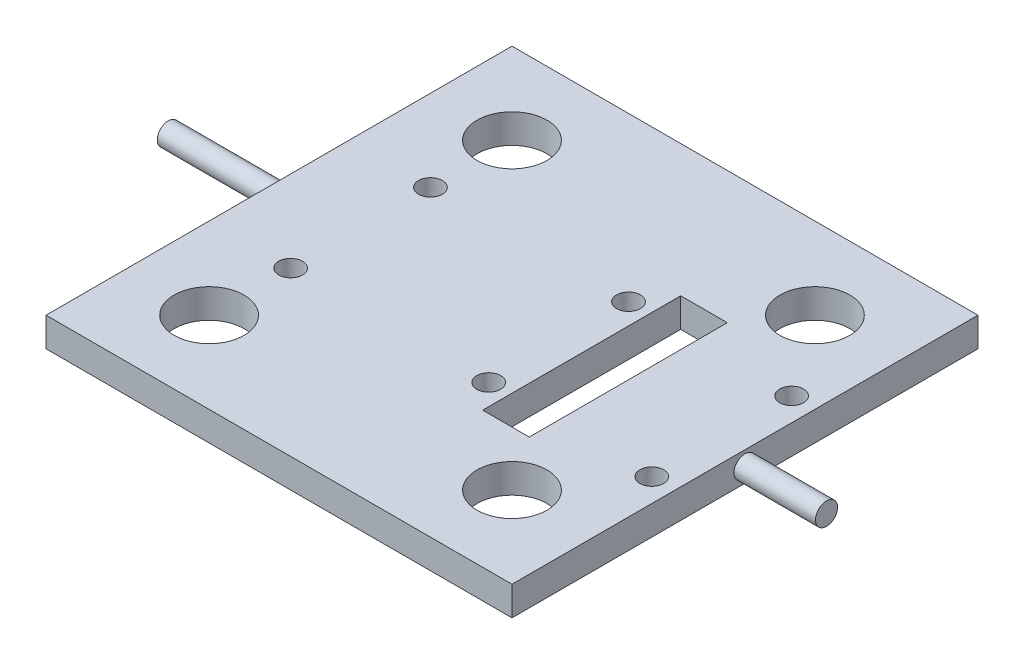
SolidWorks part; units mm, degrees
ref_plane "Front Plane" through (0, 0, 0) normal (0, 0, 1) x (1, 0, 0)
ref_plane "Top Plane" through (0, 0, 0) normal (0, 1, 0) x (1, 0, 0)
ref_plane "Right Plane" through (0, 0, 0) normal (1, 0, 0) x (0, 0, -1)
sketch "Sketch1" plane through (0, 0, 0) normal (0, 1, 0) x (1, 0, 0)
  line L1 (-25.4, -25.4) -> (25.4, -25.4)
  line L2 (-25.4, -25.4) -> (-25.4, 25.4)
  line L3 (-25.4, 25.4) -> (25.4, 25.4)
  line L4 (25.4, -25.4) -> (25.4, 25.4)
  line L5 (-25.4, -25.4) -> (25.4, 25.4) construction
  line L6 (-25.4, 25.4) -> (25.4, -25.4) construction
  point P0 (0, 0)
  dimension "D1" = 50.8
extrude "Boss-Extrude1" add sketch "Sketch1" along normal mid plane 3.175
sketch "Sketch3" plane through (25.4, 0, 0) normal (1, 0, 0) x (0, 0, -1)
  circle A0 centre (0, 0) radius 1.2065
  dimension "D1" = 2.413
extrude "Boss-Extrude2" add sketch "Sketch3" along normal blind 8.89
sketch "Sketch4" plane through (0, 1.5875, 0) normal (0, 1, 0) x (1, 0, 0)
  line L0 (25.4, 25.4) -> (-25.4, 25.4) construction
  line L1 (-25.4, 25.4) -> (-25.4, -25.4) construction
  line L2 (25.4, -25.4) -> (25.4, 25.4) construction
  line L3 (25.4, -25.4) -> (25.4, 25.4) construction
  line L4 (-25.4, -25.4) -> (25.4, -25.4) construction
  line L5 (-25.4, 25.4) -> (-25.4, -25.4) construction
  line L6 (-25.4, 0) -> (25.4, 0) construction
  line L7 (0, 25.4) -> (0, -25.4) construction
  line L8 (25.4, 25.4) -> (-25.4, 25.4) construction
  line L12 (-25.4, 25.4) -> (-25.4, -25.4) construction
  line L14 (25.4, -25.4) -> (25.4, 25.4) construction
  circle A1 centre (-16.51, 16.51) radius 3.81
  circle A2 centre (16.51, 16.51) radius 3.81
  circle A3 centre (16.51, -16.51) radius 3.81
  circle A4 centre (-16.51, -16.51) radius 3.81
  point P0 (-16.51, -7.62)
  point P1 (-16.51, 7.62)
  point P13 (22.86, 7.62)
  point P14 (22.86, -7.62)
  point P66 (0, 0)
  point P68 (-25.4, 0)
  point P71 (25.4, 0)
  dimension "D1" = 7.62
  dimension "D2" = 8.89
  dimension "D3" = 8.89
  dimension "D4" = 8.89
  dimension "D5" = 8.89
  dimension "D6" = 8.89
  dimension "D7" = 8.89
  dimension "D8" = 8.89
  dimension "D9" = 8.89
  dimension "D10" = 8.89
  dimension "D11" = 17.78
  dimension "D12" = 8.89
  dimension "D13" = 17.78
  dimension "D14" = 15.24
  dimension "D15" = 17.78
  dimension "D16" = 2.54
extrude "Cut-Extrude1" cut sketch "Sketch4" against normal through all
sketch "Sketch5" plane through (-25.4, 0, 0) normal (-1, 0, 0) x (0, 0, 1)
  circle A0 centre (0, 0) radius 1.2065
  dimension "D1" = 2.413
extrude "Boss-Extrude3" add sketch "Sketch5" along normal blind 12.065
hole_wizard "M2 Clearance Hole1" positions "Sketch6" profile "Sketch7" hole size "M2" standard "ANSI Metric" end condition through all
sketch "Sketch6" plane through (0, 1.5875, 0) normal (0, 1, 0) x (1, 0, 0)
  line L0 (25.4, -25.4) -> (25.4, 25.4) construction
  point P0 (-16.51, -7.62)
  point P3 (-16.51, 7.62)
  point P7 (5.08, -7.62)
  point P10 (5.08, 7.62)
  point P13 (22.86, 7.62)
  point P15 (22.86, -7.62)
  dimension "D1" = 2.54
  dimension "D2" = 2.54
sketch "Sketch7" plane through (-16.51, 1.5875, 7.62) normal (1, 0, 0) x (0, 0, 1)
  line L0 (0, 0) -> (0, 3.175)
  line L1 (0, 3.175) -> (1.3, 3.175)
  line L2 (1.3, 3.175) -> (1.3, 0)
  line L5 (1.3, 0) -> (0, 0)
  line L11 (0, -6.35) -> (0, 107.95) construction
  dimension "Thru Hole Dia." = 2.6
  dimension "Thru Hole Depth" = 3.175
sketch "Sketch8" plane through (0, 1.5875, 0) normal (0, 1, 0) x (1, 0, 0)
  line L0 (25.4, -25.4) -> (25.4, 25.4) construction
  line L1 (12.446, -10.5628) -> (7.366, -10.5628)
  line L2 (12.446, -10.5628) -> (12.446, 11.0272)
  line L3 (12.446, 11.0272) -> (7.366, 11.0272)
  line L4 (7.366, -10.5628) -> (7.366, 11.0272)
  line L5 (12.446, -10.5628) -> (7.366, 11.0272) construction
  line L6 (12.446, 11.0272) -> (7.366, -10.5628) construction
  point P0 (9.906, 0.2322)
  dimension "D1" = 5.08
  dimension "D2" = 21.59
  dimension "D3" = 12.954
extrude "Cut-Extrude2" cut sketch "Sketch8" against normal up to next
